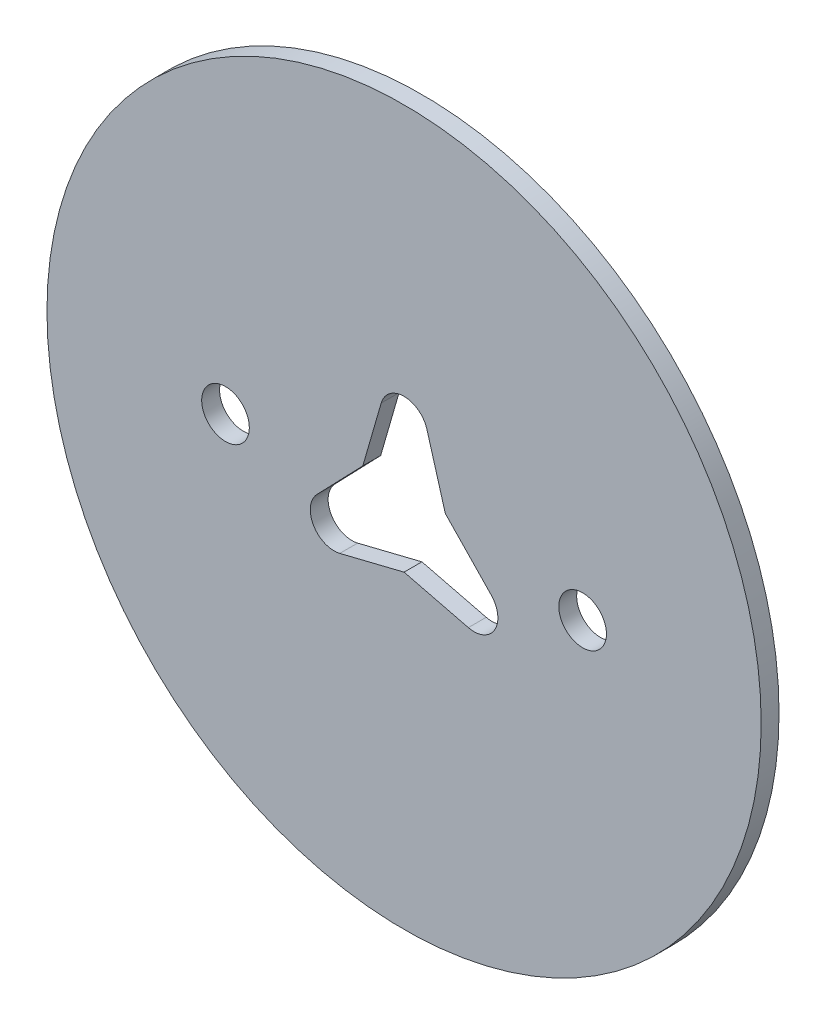
SolidWorks part; units mm, degrees
material "Chrome Stainless Steel"
ref_plane "Front Plane" through (0, 0, 0) normal (0, 0, 1) x (1, 0, 0)
ref_plane "Top Plane" through (0, 0, 0) normal (0, 1, 0) x (1, 0, 0)
ref_plane "Right Plane" through (0, 0, 0) normal (1, 0, 0) x (0, 0, -1)
sketch "Sketch1" plane through (0, 0, 0) normal (0, 0, 1) x (1, 0, 0)
  line L0 (0, 0) -> (30, 0) construction
  line L1 (0, 0) -> (-30, 0) construction
  circle A0 centre (0, 0) radius 30
  circle A1 centre (15, 0) radius 2
  circle A2 centre (-15, 0) radius 2
  dimension "D1" = 60
  dimension "D4" = 4
  dimension "D2" = 15
  dimension "D3" = 15
extrude "Boss-Extrude1" add sketch "Sketch1" along normal blind 1.5
sketch "Sketch2" plane through (0, 0, 0) normal (0, 0, -1) x (-1, 0, 0)
  line L0 (0, 0) -> (0, 14) construction
  line L1 (0, 0) -> (-12.1244, -7) construction
  line L2 (0, 0) -> (12.1244, -7)
  line L3 (-12.1244, -7) -> (-3.4641, 2)
  line L4 (-3.4641, 2) -> (0, 14)
  line L5 (0, 14) -> (3.4641, 2)
  line L6 (0, -4) -> (12.1244, -7)
  line L7 (-12.1244, -7) -> (0, -4)
  line L8 (3.4641, 2) -> (12.1244, -7)
  circle A0 centre (0, 0) radius 14 construction
  circle A1 centre (0, 0) radius 10 construction
  circle A2 centre (0, 0) radius 4 construction
  dimension "D1" = 28
  dimension "D2" = 20
  dimension "D5" = 8
  dimension "D3" = 120
  dimension "D4" = 120
extrude "Cut-Extrude1" cut sketch "Sketch2" against normal blind 10 contours L0 A1 | A1 | A1 | A1 | L0 A1 | L0 A1 A0 | A1 L0 A0 | A1 A0 | L6 L7 L3 L4 L5 L8
fillet "Fillet1" radius 2 3 edges at (12.1244, -7, 0.75) (-12.1244, -7, 0.75) (0, 14, 0.75)
equation "\"D3@Sketch1\"=\"D2@Sketch1\""
